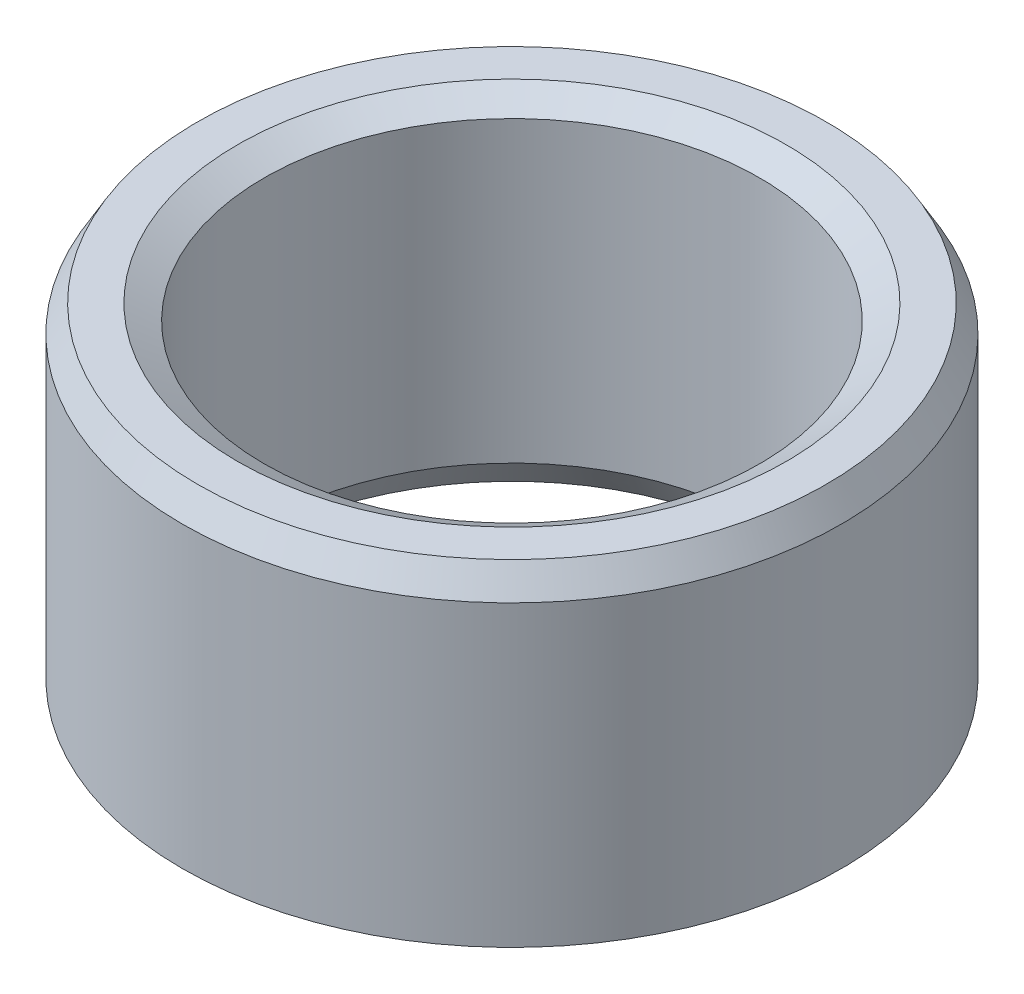
SolidWorks part; units mm, degrees
ref_plane "Front Plane" through (0, 0, 0) normal (0, 0, 1) x (1, 0, 0)
ref_plane "Top Plane" through (0, 0, 0) normal (0, 1, 0) x (1, 0, 0)
ref_plane "Right Plane" through (0, 0, 0) normal (1, 0, 0) x (0, 0, -1)
sketch "Sketch1" plane through (0, 0, 0) normal (0, 1, 0) x (1, 0, 0)
  circle A0 centre (0, 0) radius 30
  dimension "SLEEVE_OD" = 60
extrude "Boss-Extrude1" add sketch "Sketch1" along normal blind 30.9848
sketch "Sketch2" plane through (0, 0, 0) normal (0, 1, 0) x (1, 0, 0)
  circle A0 centre (0, 0) radius 22.5516
  dimension "BORE_D" = 45.1031
extrude "Cut-Extrude1" cut sketch "Sketch2" along normal through all
chamfer "Chamfer1" distance 2.4253 angle 30 4 edges at (0, 30.9848, 22.5516) (0, 0, 22.5516) (0, 0, 30) (0, 30.9848, 30) first distance on face at (0, 30.9848, 22.5516) first distance on face at (0, 0, 22.5516) first distance on face at (0, 30.9848, 30)
